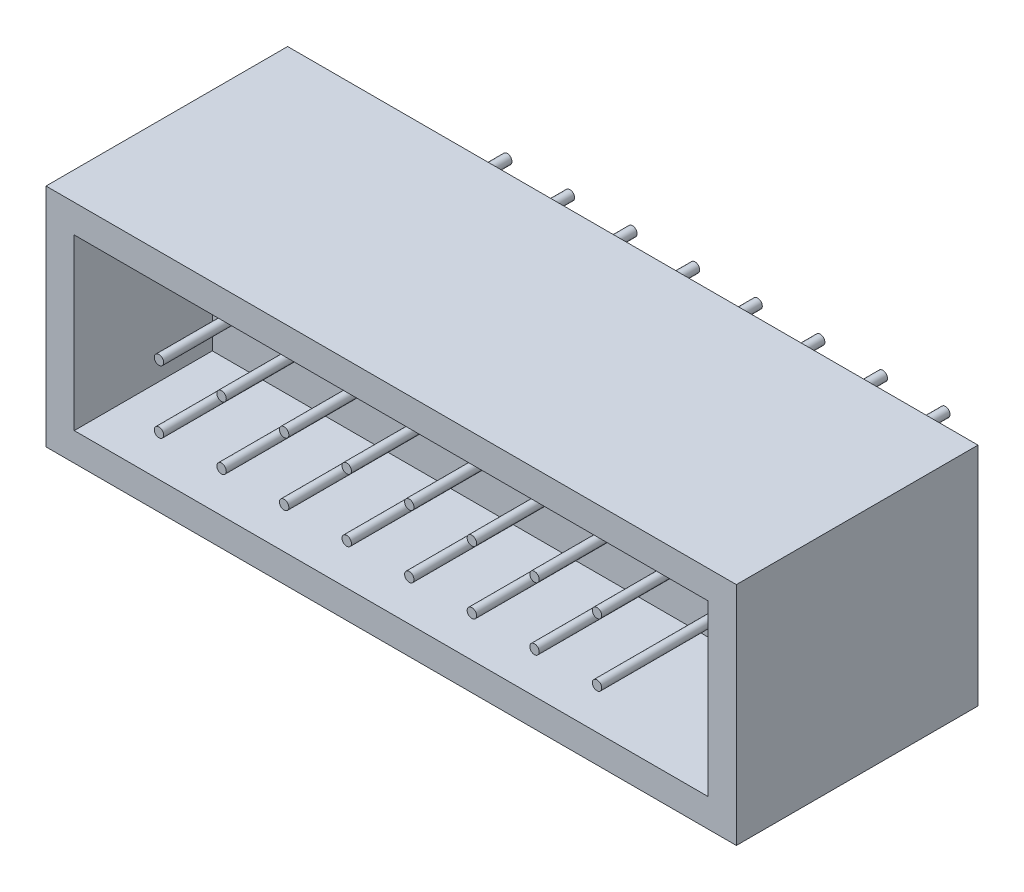
SolidWorks part; units mm, degrees
ref_plane "Front" through (0, 0, 0) normal (0, 0, 1) x (1, 0, 0)
ref_plane "Top" through (0, 0, 0) normal (0, 1, 0) x (1, 0, 0)
ref_plane "Right" through (0, 0, 0) normal (1, 0, 0) x (0, 0, -1)
sketch "Sketch1" plane through (0, 0, 0) normal (0, 0, 1) x (1, 0, 0)
  line L1 (0, 0) -> (27.94, 0)
  line L2 (0, 0) -> (0, -9.144)
  line L3 (0, -9.144) -> (27.94, -9.144)
  line L4 (27.94, 0) -> (27.94, -9.144)
  dimension "D1" = 27.94
  dimension "D2" = 9.144
extrude "Extrude1" add sketch "Sketch1" along normal blind 9.779
sketch "Sketch2" plane through (0, 0, 9.779) normal (0, 0, 1) x (1, 0, 0)
  line L0 (27.94, -9.144) -> (27.94, 0) construction
  line L1 (1.143, -1.143) -> (26.797, -1.143)
  line L2 (1.143, -1.143) -> (1.143, -8.001)
  line L3 (1.143, -8.001) -> (26.797, -8.001)
  line L4 (26.797, -1.143) -> (26.797, -8.001)
  line L5 (0, 0) -> (0, -9.144) construction
  line L6 (27.94, 0) -> (0, 0) construction
  line L7 (0, -9.144) -> (27.94, -9.144) construction
  dimension "D1" = 1.143
  dimension "D2" = 1.143
  dimension "D3" = 1.143
  dimension "D4" = 1.143
extrude "Cut-Extrude1" cut sketch "Sketch2" against normal blind 5.588
sketch "Sketch4" plane through (0, 0, 4.191) normal (0, 0, 1) x (1, 0, 0)
  line L0 (0, -9.144) -> (27.94, -9.144) construction
  line L1 (1.143, -1.143) -> (1.143, -8.001) construction
  line L2 (5.08, -5.842) -> (7.6127, -5.842) construction
  line L3 (5.08, -5.842) -> (5.08, -3.302) construction
  line L4 (26.797, -8.001) -> (26.797, -1.143) construction
  circle A0 centre (5.08, -5.842) radius 0.1905
  circle A1 centre (7.6127, -5.842) radius 0.1905
  circle A2 centre (10.1455, -5.842) radius 0.1905
  circle A3 centre (12.6782, -5.842) radius 0.1905
  circle A4 centre (15.211, -5.842) radius 0.1905
  circle A5 centre (17.7437, -5.842) radius 0.1905
  circle A6 centre (20.2765, -5.842) radius 0.1905
  circle A7 centre (22.8092, -5.842) radius 0.1905
  circle A8 centre (5.08, -3.302) radius 0.1905
  circle A9 centre (7.6127, -3.302) radius 0.1905
  circle A10 centre (10.1455, -3.302) radius 0.1905
  circle A11 centre (12.6782, -3.302) radius 0.1905
  circle A12 centre (15.211, -3.302) radius 0.1905
  circle A13 centre (17.7437, -3.302) radius 0.1905
  circle A14 centre (20.2765, -3.302) radius 0.1905
  circle A15 centre (22.8092, -3.302) radius 0.1905
  dimension "D1" = 0.381
  dimension "D2" = 3.302
  dimension "D3" = 3.937
  dimension "D4" = 90
  dimension "D5" = 3.9878
extrude "Extrude3" add sketch "Sketch4" along normal blind 6.096 and the other way blind 8
